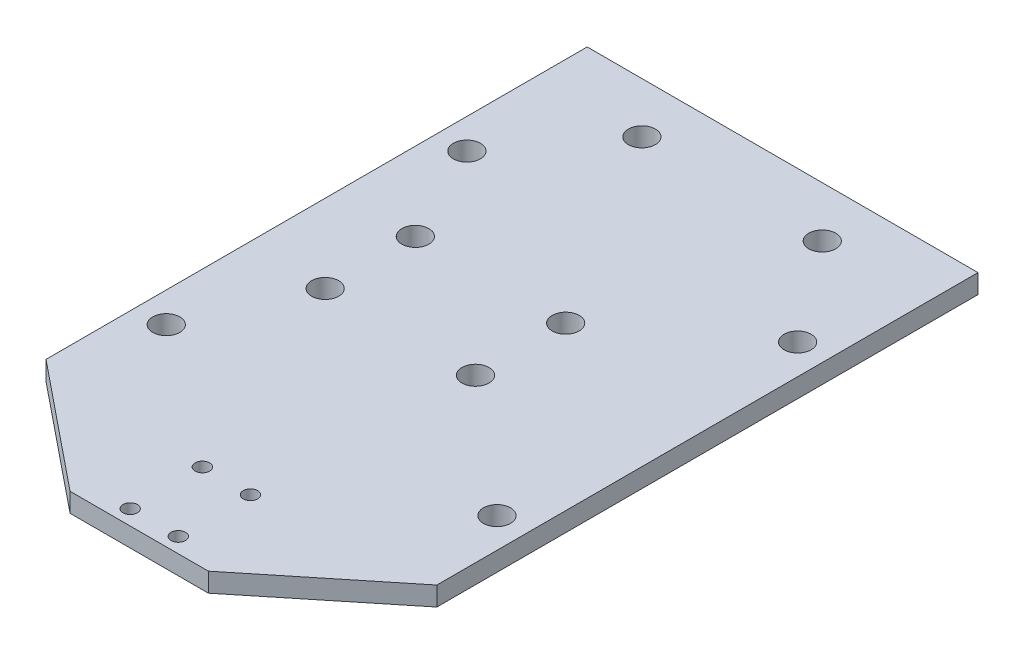
SolidWorks part; units mm, degrees
material "6061-T6 (SS)"
ref_plane "Front Plane" through (0, 0, 0) normal (0, 0, 1) x (1, 0, 0)
ref_plane "Top Plane" through (0, 0, 0) normal (0, 1, 0) x (1, 0, 0)
ref_plane "Right Plane" through (0, 0, 0) normal (1, 0, 0) x (0, 0, -1)
sketch "Sketch1" plane through (0, 0, 0) normal (0, 1, 0) x (1, 0, 0)
  line L0 (-11.5, -62) -> (-32.5, -45)
  line L1 (32.5, -45) -> (-32.5, -45)
  line L2 (32.5, -45) -> (32.5, 45)
  line L3 (32.5, 45) -> (-32.5, 45)
  line L4 (-32.5, -45) -> (-32.5, 45)
  line L5 (32.5, -45) -> (-32.5, 45) construction
  line L6 (32.5, 45) -> (-32.5, -45) construction
  line L7 (-11.5, -45) -> (11.5, -45)
  line L8 (-11.5, -45) -> (-11.5, -62)
  line L9 (-11.5, -62) -> (11.5, -62)
  line L10 (11.5, -45) -> (11.5, -62)
  line L11 (11.5, -62) -> (32.5, -45)
  line L12 (-32.5, -45) -> (32.5, -45)
  line L13 (11.5, -62) -> (-11.5, -62)
  point P0 (0, 0)
  point P10 (0, -62)
  dimension "D1" = 90
  dimension "D2" = 65
  dimension "D3" = 23
  dimension "D4" = 17
  dimension "D5" = 32.5
extrude "Boss-Extrude1" add sketch "Sketch1" along normal mid plane 3.175 contours L8 L1 L0 | L10 L11 L1 | L4 L1 L2 L3 | L10 L1 L8 L9 region at (-18.5, 0, 50.6667) region at (0, 0, 53.5) region at (0, 0, 0) region at (18.5, 0, 50.6667)
sketch "Sketch4" plane through (0, 1.5875, 0) normal (0, 1, 0) x (1, 0, 0)
  line L0 (-11.5, -62) -> (11.5, -62) construction
  point P0 (-4, -59.5)
  point P2 (4, -59.5)
  point P4 (4, -47.5)
  point P6 (-4, -47.5)
  point P16 (0, -62)
  dimension "D1" = 8
  dimension "D2" = 12
  dimension "D3" = 4
  dimension "D4" = 2.5
hole_wizard "M2 Clearance Hole1" positions "Sketch4" profile "Sketch3" hole size "M2" standard "ANSI Metric" end condition through all
sketch "Sketch3" plane through (-4, 1.5875, 59.5) normal (1, 0, 0) x (0, 0, 1)
  line L0 (0, 0) -> (0, 3.175)
  line L1 (0, 3.175) -> (1.2, 3.175)
  line L2 (1.2, 3.175) -> (1.2, 0)
  line L5 (1.2, 0) -> (0, 0)
  line L11 (0, -6.35) -> (0, 107.95) construction
  dimension "Thru Hole Dia." = 2.4
  dimension "Thru Hole Depth" = 3.175
sketch "Sketch7" plane through (0, 1.5875, 0) normal (0, 1, 0) x (1, 0, 0)
  line L0 (-32.5, -45) -> (-32.5, 45) construction
  line L1 (32.5, -45) -> (32.5, 45) construction
  line L2 (32.5, 45) -> (-32.5, 45) construction
  point P0 (-27.5, 20)
  point P2 (27.5, 20)
  point P4 (27.5, -30)
  point P6 (-27.5, -30)
  dimension "D1" = 5
  dimension "D2" = 5
  dimension "D3" = 25
  dimension "D4" = 50
hole_wizard "M4 Clearance Hole1" positions "Sketch7" profile "Sketch6" hole size "M4" standard "ANSI Metric" end condition through all
sketch "Sketch6" plane through (-27.5, 1.5875, -20) normal (1, 0, 0) x (0, 0, 1)
  line L0 (0, 0) -> (0, 3.175)
  line L1 (0, 3.175) -> (2.25, 3.175)
  line L2 (2.25, 3.175) -> (2.25, 0)
  line L5 (2.25, 0) -> (0, 0)
  line L11 (0, -6.35) -> (0, 107.95) construction
  dimension "Thru Hole Dia." = 4.5
  dimension "Thru Hole Depth" = 3.175
hole_wizard "M4 Clearance Hole2" positions "Sketch10" profile "Sketch9" hole size "M4" standard "ANSI Metric" end condition through all
sketch "Sketch10" plane through (0, 1.5875, 0) normal (0, 1, 0) x (1, 0, 0)
  point P0 (-19.5, -11.575)
  point P3 (-19.5, 3.425)
  point P6 (5.5, 3.425)
  point P9 (5.5, -11.575)
sketch "Sketch9" plane through (-19.5, 1.5875, 11.575) normal (1, 0, 0) x (0, 0, 1)
  line L0 (0, 0) -> (0, 3.175)
  line L1 (0, 3.175) -> (2.25, 3.175)
  line L2 (2.25, 3.175) -> (2.25, 0)
  line L5 (2.25, 0) -> (0, 0)
  line L11 (0, -6.35) -> (0, 107.95) construction
  dimension "Thru Hole Dia." = 4.5
  dimension "Thru Hole Depth" = 3.175
hole_wizard "M4 Clearance Hole3" positions "Sketch13" profile "Sketch12" hole size "M4" standard "ANSI Metric" end condition through all
sketch "Sketch13" plane through (0, -1.5875, 0) normal (0, -1, 0) x (-1, 0, 0)
  point P0 (-15, 36.6)
  point P3 (15, 36.6)
sketch "Sketch12" plane through (15, -1.5875, -36.6) normal (1, 0, 0) x (0, 0, -1)
  line L0 (0, 0) -> (0, 3.175)
  line L1 (0, 3.175) -> (2.25, 3.175)
  line L2 (2.25, 3.175) -> (2.25, 0)
  line L5 (2.25, 0) -> (0, 0)
  line L11 (0, -6.35) -> (0, 107.95) construction
  dimension "Thru Hole Dia." = 4.5
  dimension "Thru Hole Depth" = 3.175
